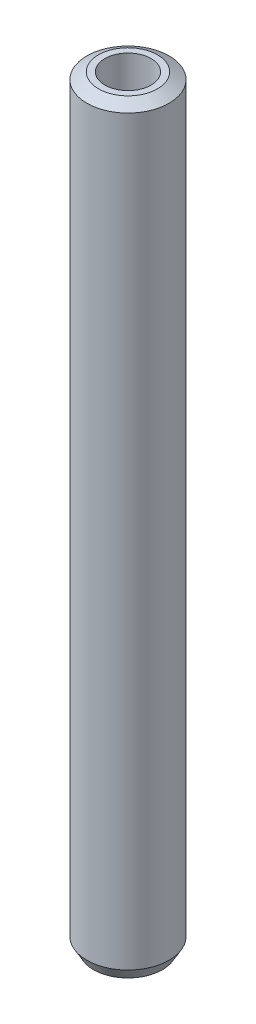
SolidWorks part; units mm, degrees
ref_plane "Front Plane" through (0, 0, 0) normal (0, 0, 1) x (1, 0, 0)
ref_plane "Top Plane" through (0, 0, 0) normal (0, 1, 0) x (1, 0, 0)
ref_plane "Right Plane" through (0, 0, 0) normal (1, 0, 0) x (0, 0, -1)
sketch "Sketch1" plane through (0, 0, 0) normal (0, 1, 0) x (1, 0, 0)
  circle A0 centre (0, 0) radius 20
  dimension "SHAFT_OD" = 40
extrude "Boss-Extrude1" add sketch "Sketch1" along normal blind 370.1223
sketch "Sketch2" plane through (0, 0, 0) normal (0, 1, 0) x (1, 0, 0)
  circle A0 centre (0, 0) radius 11.2246
  dimension "BORE_D" = 22.4491
extrude "Cut-Extrude1" cut sketch "Sketch2" along normal through all
chamfer "Chamfer1" distance 3.259 angle 60 2 edges at (0, 370.1223, 20) (0, 0, 20) first distance on face at (0, 370.1223, 20) first distance on face at (0, 0, 11.2246)
